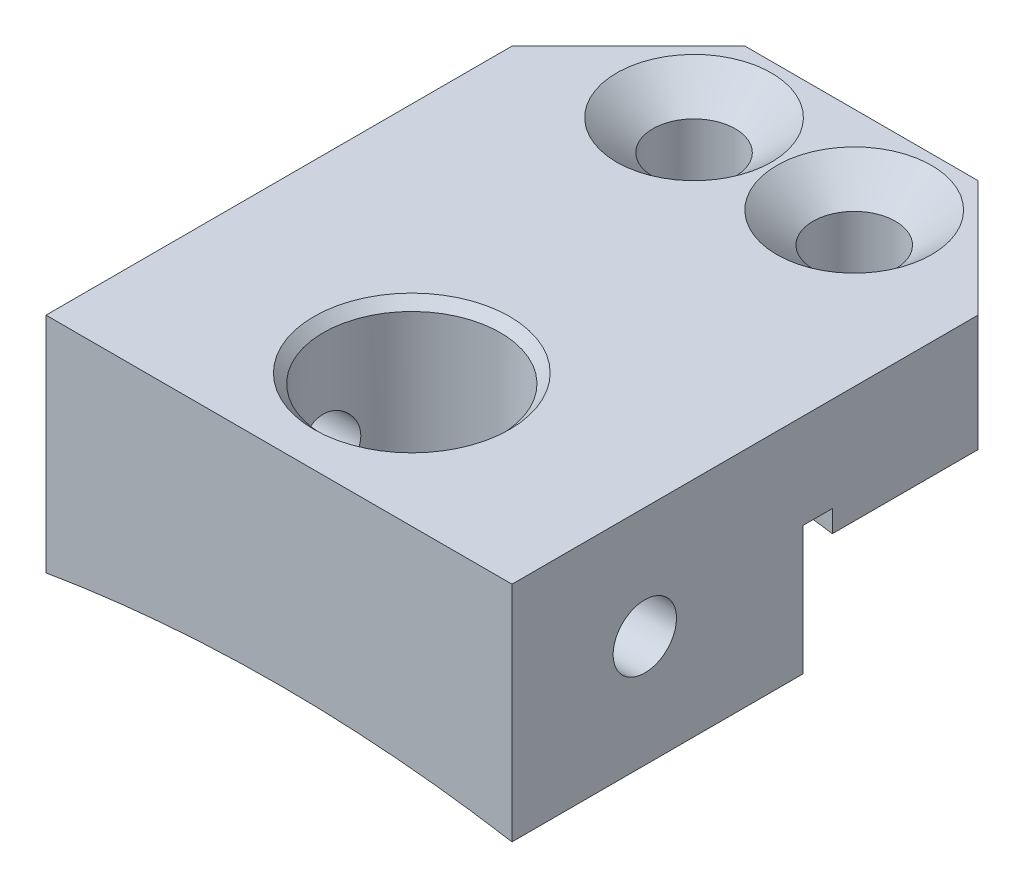
SolidWorks part; units mm, degrees
ref_plane "Front Plane" through (0, 0, 0) normal (0, 0, 1) x (1, 0, 0)
ref_plane "Top Plane" through (0, 0, 0) normal (0, 1, 0) x (1, 0, 0)
ref_plane "Right Plane" through (0, 0, 0) normal (1, 0, 0) x (0, 0, -1)
sketch "Sketch1" plane through (0, 0, 0) normal (0, 1, 0) x (1, 0, 0)
  line L0 (-12.7, 15.875) -> (12.7, -15.875) construction
  line L1 (-12.7, 15.875) -> (12.7, 15.875)
  line L2 (-12.7, 15.875) -> (-12.7, -15.875)
  line L3 (-12.7, -15.875) -> (12.7, -15.875)
  line L4 (12.7, 15.875) -> (12.7, -15.875)
  point P4 (0, 0)
  dimension "D1" = 25.4
  dimension "D2" = 31.75
extrude "Boss-Extrude1" add sketch "Sketch1" along normal blind 6.35
sketch "Sketch2" plane through (0, 0, 15.875) normal (0, 0, 1) x (1, 0, 0)
  line L0 (-12.7, 0) -> (12.7, 0)
  arc A0 (-12.7, 0) -> (12.7, 0) centre (0, -80.9502) cw
  dimension "D1" = 81.9404
extrude "Cut-Extrude1" cut sketch "Sketch2" against normal through all
sketch "Sketch3" plane through (0, 0, 15.875) normal (0, 0, 1) x (1, 0, 0)
  line L0 (-12.7, 6.35) -> (12.7, 6.35)
  line L1 (12.7, 6.35) -> (12.7, -5.816)
  line L2 (-12.7, 6.35) -> (-12.7, -5.816)
  arc A0 (-12.7, -5.816) -> (12.7, -5.816) centre (0, -80.9502) cw
  arc A1 (12.7, 0) -> (-12.7, 0) centre (0, -80.9502) ccw construction
  dimension "D1" = 76.2
extrude "Boss-Extrude2" add sketch "Sketch3" against normal blind 15.875
sketch "Sketch4" plane through (-12.7, 0, 0) normal (-1, 0, 0) x (0, 0, 1)
  line L1 (0, 0) -> (-1.5875, 0)
  line L2 (0, 0) -> (0, 1.1906)
  line L3 (0, 1.1906) -> (-1.5875, 1.1906)
  line L4 (-1.5875, 0) -> (-1.5875, 1.1906)
  dimension "D1" = 1.5875
  dimension "D2" = 1.1906
extrude "Cut-Extrude2" cut sketch "Sketch4" against normal through all
chamfer "Chamfer1" distance 6.35 angle 45 2 edges at (-12.7, 3.175, -15.875) (12.7, 3.175, -15.875)
sketch "Sketch5" plane through (0, 6.35, 0) normal (0, 1, 0) x (1, 0, 0)
  line L0 (-12.7, 9.525) -> (-12.7, -15.875) construction
  line L1 (-12.7, -15.875) -> (12.7, -15.875) construction
  circle A1 centre (0, -8.636) radius 1.524
  dimension "D1" = 3.048
  dimension "D2" = 12.7
  dimension "D3" = 7.239
extrude "Cut-Extrude3" cut sketch "Sketch5" against normal through all
hole_wizard "CSK for #8 Flat Head Machine Screw (100)1" positions "Sketch6" profile "Sketch7" countersink size "#8" standard "ANSI Inch" end condition through all
sketch "Sketch6" plane through (0, 6.35, 0) normal (0, 1, 0) x (1, 0, 0)
  line L0 (0, 15.875) -> (0, 4.8645) construction
  line L1 (6.35, 15.875) -> (-6.35, 15.875) construction
  point P0 (-4.3656, 11.1125)
  point P18 (4.3656, 11.1125)
  dimension "D1" = 4.7625
  dimension "D2" = 4.3656
sketch "Sketch7" plane through (-4.3656, 6.35, -11.1125) normal (1, 0, 0) x (0, 0, 1)
  line L0 (0, 0) -> (0, 12.166)
  line L1 (0, 12.166) -> (2.2479, 12.166)
  line L2 (2.2479, 12.166) -> (2.2479, 1.6518)
  line L3 (2.2479, 1.6518) -> (4.2164, 0)
  line L5 (4.2164, 0) -> (0, 0)
  line L6 (-2.2479, 1.6518) -> (-4.2164, 0) construction
  line L11 (0, -6.35) -> (0, 107.95) construction
  dimension "Thru Hole Dia." = 4.4958
  dimension "Thru Hole Depth" = 12.166
  dimension "Near C'Sink Dia." = 8.4328
  dimension "Near C'Sink Angle" = 100
sketch "Sketch8" plane through (0, 6.35, 0) normal (0, 1, 0) x (1, 0, 0)
  circle A0 centre (0, -8.636) radius 4.826
  dimension "D1" = 9.652
extrude "Cut-Extrude4" cut sketch "Sketch8" against normal through all
chamfer "Chamfer2" distance 0.508 angle 45 1 edges at (0, 6.35, 13.462)
hole_wizard "#8-32 Tapped Hole1" positions "Sketch11" profile "Sketch12" tap size "#8-32" standard "ANSI Inch" end condition through all
sketch "Sketch11" plane through (-12.7, 0, 0) normal (-1, 0, 0) x (0, 0, 1)
  line L0 (13.462, 5.842) -> (3.81, 5.842) construction
  line L1 (13.462, 5.842) -> (3.81, 5.842)
  line L2 (8.636, 6.35) -> (8.636, -5.816) construction
  line L3 (-9.525, 6.35) -> (15.875, 6.35) construction
  line L4 (0, -5.816) -> (15.875, -5.816) construction
  point P0 (8.636, 0.267)
  point P12 (8.636, 5.842)
  point P14 (8.636, 0.267)
cosmetic thread "Hole Thread2"
sketch "Sketch12" plane through (-12.7, 0.267, 8.636) normal (0, 1, 0) x (0, 0, 1)
  line L0 (0, 0) -> (0, 25.4)
  line L1 (0, 25.4) -> (1.7272, 25.4)
  line L2 (1.7272, 25.4) -> (1.7272, 0)
  line L5 (1.7272, 0) -> (0, 0)
  line L11 (0, -6.35) -> (0, 107.95) construction
  dimension "Thru Tap Drill Dia." = 3.4544
  dimension "Thru Tap Drill Depth" = 25.4
